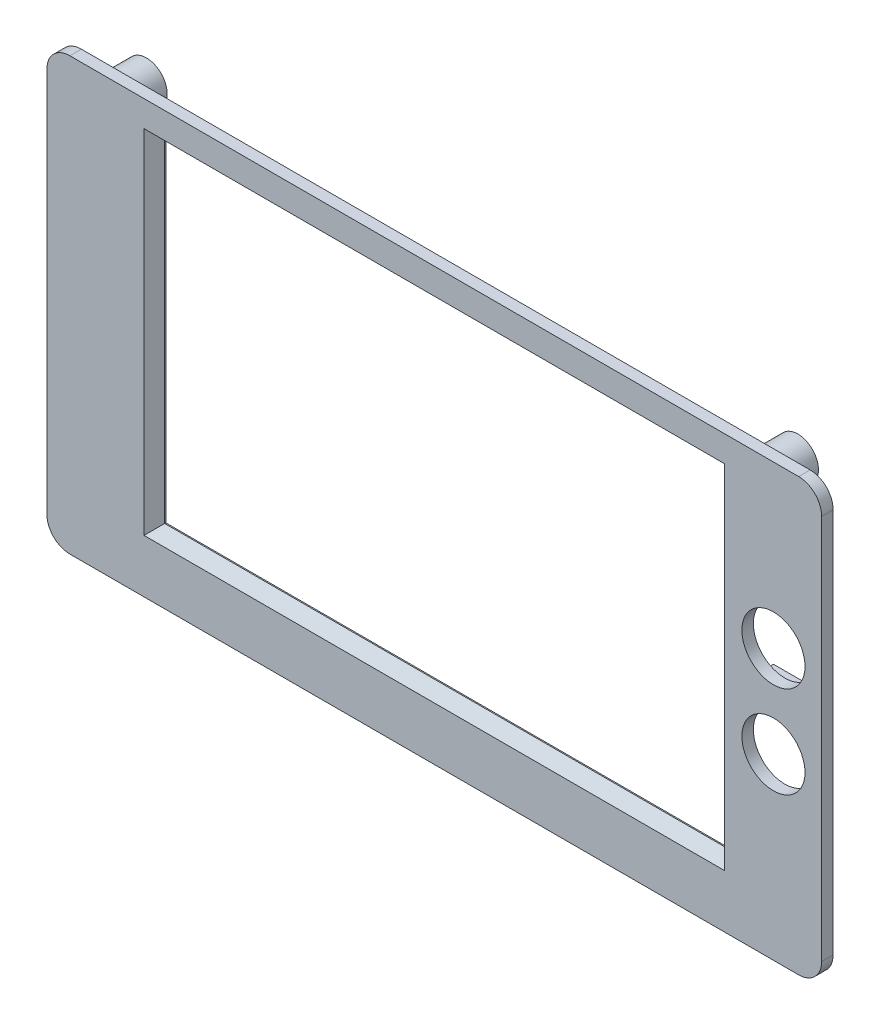
SolidWorks part; units mm, degrees
ref_plane "Спереди" through (0, 0, 0) normal (0, 0, 1) x (1, 0, 0)
ref_plane "Сверху" through (0, 0, 0) normal (0, 1, 0) x (1, 0, 0)
ref_plane "Справа" through (0, 0, 0) normal (1, 0, 0) x (0, 0, -1)
sketch "Эскиз2" plane through (0, 0, 0) normal (0, 0, 1) x (1, 0, 0)
  line L0 (47.98, -25.72) -> (47.98, 30.47)
  line L1 (47.98, 30.47) -> (-47.98, 30.47)
  line L2 (-47.98, 30.47) -> (-47.98, -25.72)
  line L3 (-47.98, -25.72) -> (47.98, -25.72)
  line L4 (-52.73, -33.72) -> (52.73, -33.72)
  line L5 (-52.73, 33.72) -> (-52.73, -33.72)
  line L6 (52.73, 33.72) -> (-52.73, 33.72)
  line L7 (52.73, -33.72) -> (52.73, 33.72)
  line L8 (57.5, 37) -> (-57.5, 37)
  line L9 (60, -34.5) -> (60, 34.5)
  line L10 (-60, 34.5) -> (-60, -34.5)
  line L11 (-57.5, -37) -> (57.5, -37)
  circle A0 centre (56.75, 33.75) radius 1.6
  circle A1 centre (56.75, -33.75) radius 1.6
  arc A2 (60, 34.5) -> (57.5, 37) centre (57.5, 34.5) ccw
  arc A3 (-57.5, 37) -> (-60, 34.5) centre (-57.5, 34.5) ccw
  circle A4 centre (-56.75, 33.75) radius 1.6
  arc A5 (-60, -34.5) -> (-57.5, -37) centre (-57.5, -34.5) ccw
  circle A6 centre (-56.75, -33.75) radius 1.6
  arc A7 (57.5, -37) -> (60, -34.5) centre (57.5, -34.5) ccw
sketch "Эскиз3" plane through (0, 0, 0) normal (0, 0, 1) x (1, 0, 0)
  line L0 (-57.5, -37) -> (57.5, -37) construction
  line L1 (-60, 34.5) -> (-60, -34.5) construction
  line L2 (57.5, 37) -> (-57.5, 37) construction
  line L3 (60, -34.5) -> (60, 34.5) construction
  line L4 (-47.98, -25.72) -> (47.98, -25.72) construction
  line L5 (47.98, -25.72) -> (47.98, 30.47) construction
  line L6 (47.98, 30.47) -> (-47.98, 30.47) construction
  line L7 (-47.98, 30.47) -> (-47.98, -25.72) construction
  line L8 (-57.5, -37) -> (57.5, -37)
  line L9 (-60, 34.5) -> (-60, -34.5)
  line L10 (57.5, 37) -> (-57.5, 37)
  line L11 (60, -34.5) -> (60, 34.5)
  line L12 (-47.98, -25.72) -> (47.98, -25.72)
  line L13 (47.98, -25.72) -> (47.98, 30.47)
  line L14 (47.98, 30.47) -> (-47.98, 30.47)
  line L15 (-47.98, 30.47) -> (-47.98, -25.72)
  arc A0 (-60, -34.5) -> (-57.5, -37) centre (-57.5, -34.5) ccw construction
  arc A1 (-60, -34.5) -> (-57.5, -37) centre (-57.5, -34.5) ccw
  arc A2 (57.5, -37) -> (60, -34.5) centre (57.5, -34.5) ccw construction
  arc A3 (57.5, -37) -> (60, -34.5) centre (57.5, -34.5) ccw
  arc A4 (60, 34.5) -> (57.5, 37) centre (57.5, 34.5) ccw construction
  arc A5 (60, 34.5) -> (57.5, 37) centre (57.5, 34.5) ccw
  arc A6 (-57.5, 37) -> (-60, 34.5) centre (-57.5, 34.5) ccw construction
  arc A7 (-57.5, 37) -> (-60, 34.5) centre (-57.5, 34.5) ccw
extrude "Бобышка-Вытянуть2" add sketch "Эскиз3" along normal blind 2
sketch "Эскиз4" plane through (0, 0, 2) normal (0, 0, 1) x (1, 0, 0)
  line L0 (-47.98, 30.47) -> (-47.98, -25.72) construction
  line L1 (-47.98, -25.72) -> (47.98, -25.72) construction
  line L2 (47.98, -25.72) -> (47.98, 30.47) construction
  line L3 (47.98, 30.47) -> (-47.98, 30.47) construction
  line L4 (-47.98, 30.47) -> (-47.98, -25.72)
  line L5 (-47.98, -25.72) -> (47.98, -25.72)
  line L6 (47.98, -25.72) -> (47.98, 30.47)
  line L7 (47.98, 30.47) -> (-47.98, 30.47)
extrude "Вырез-Вытянуть-Тонкостенный1" cut sketch "Эскиз4" against normal blind 2 thin thin type one direction wall 0.8
sketch "Эскиз5" plane through (0, 0, 0) normal (0, 0, -1) x (-1, 0, 0)
  circle A0 centre (56.75, 33.75) radius 2.4
  circle A1 centre (-56.75, 33.75) radius 2.4
  circle A2 centre (-56.75, -33.75) radius 2.4
  circle A3 centre (56.75, -33.75) radius 2.4
  dimension "D1" = 4.8
extrude "Вытянуть-Тонкостенный1" add sketch "Эскиз5" along normal blind 4.6 thin thin type one direction wall 1.2
sketch "Эскиз7" plane through (0, 0, 2) normal (0, 0, 1) x (1, 0, 0)
  line L4 (-57.5, -37) -> (57.5, -37)
  line L5 (60, -34.5) -> (60, 34.5)
  line L6 (57.5, 37) -> (-57.5, 37)
  line L7 (-60, 34.5) -> (-60, -34.5)
  line L8 (-57.5, -37) -> (57.5, -37)
  line L9 (60, -34.5) -> (60, 34.5)
  line L10 (57.5, 37) -> (-57.5, 37)
  line L11 (-60, 34.5) -> (-60, -34.5)
  arc A4 (-60, -34.5) -> (-57.5, -37) centre (-57.5, -34.5) ccw
  arc A5 (57.5, -37) -> (60, -34.5) centre (57.5, -34.5) ccw
  arc A6 (60, 34.5) -> (57.5, 37) centre (57.5, 34.5) ccw
  arc A7 (-57.5, 37) -> (-60, 34.5) centre (-57.5, 34.5) ccw
  arc A8 (-60, -34.5) -> (-57.5, -37) centre (-57.5, -34.5) ccw
  arc A9 (57.5, -37) -> (60, -34.5) centre (57.5, -34.5) ccw
  arc A10 (60, 34.5) -> (57.5, 37) centre (57.5, 34.5) ccw
  arc A11 (-57.5, 37) -> (-60, 34.5) centre (-57.5, 34.5) ccw
  dimension "D1" = 0
extrude "Вытянуть-Тонкостенный3" add sketch "Эскиз7" against normal blind 2 thin thin type one direction wall 0.6
chamfer "Фаска1" distance 1.8 angle 45 4 edges at (0, -26.52, 2) (48.78, 2.375, 2) (0, 31.27, 2) (-48.78, 2.375, 2)
sketch "Эскиз8" plane through (0, 0, 2) normal (0, 0, 1) x (1, 0, 0)
  line L1 (57.5, 37.6) -> (67.5, 37.6)
  line L2 (57.5, 37.6) -> (57.5, -37.6)
  line L3 (57.5, -37.6) -> (67.5, -37.6)
  line L4 (67.5, 37.6) -> (67.5, -37.6)
  line L5 (-57.5, 37.6) -> (-67.5, 37.6)
  line L6 (-57.5, 37.6) -> (-57.5, -37.6)
  line L7 (-57.5, -37.6) -> (-67.5, -37.6)
  line L8 (-67.5, 37.6) -> (-67.5, -37.6)
  dimension "D1" = 10
  dimension "D2" = 10
extrude "Бобышка-Вытянуть3" add sketch "Эскиз8" against normal blind 2
fillet "Скругление1" radius 4 4 edges at (67.5, -37.6, 1) (-67.5, -37.6, 1) (67.5, 37.6, 1) (-67.5, 37.6, 1)
sketch "Эскиз9" plane through (0, 0, 2) normal (0, 0, 1) x (1, 0, 0)
  line L0 (67.5, -33.6) -> (67.5, 33.6) construction
  line L1 (-48.78, -26.52) -> (48.78, -26.52) construction
  circle A0 centre (59.1, 9.48) radius 5.5
  circle A1 centre (59.1, -6.52) radius 5.5
  dimension "D1" = 11
  dimension "D2" = 11
  dimension "D3" = 8.4
  dimension "D4" = 8.4
  dimension "D5" = 16
  dimension "D6" = 20
extrude "Вырез-Вытянуть1" cut sketch "Эскиз9" against normal blind 2
sketch "Эскиз11" plane through (0, 0, 0) normal (0, 0, -1) x (-1, 0, 0)
  circle A1 centre (-56.75, 33.75) radius 2.4
  circle A2 centre (-56.75, 33.75) radius 2.4
  circle A3 centre (56.75, 33.75) radius 2.4
  circle A4 centre (56.75, 33.75) radius 2.4
  circle A5 centre (56.75, -33.75) radius 2.4
  circle A6 centre (56.75, -33.75) radius 2.4
  circle A7 centre (-56.75, -33.75) radius 2.4
  circle A8 centre (-56.75, -33.75) radius 2.4
  dimension "D1" = 0
  dimension "D2" = 0
  dimension "D3" = 0
  dimension "D4" = 0
extrude "Вытянуть-Тонкостенный4" add sketch "Эскиз11" along normal blind 4.6 thin thin type one direction reverse wall 1.4
sketch "Эскиз14" plane through (0, 0, 0) normal (0, 0, -1) x (-1, 0, 0)
  line L1 (-64.1, 18.48) -> (-54.1, 18.48)
  line L2 (-64.1, 18.48) -> (-64.1, 17.48)
  line L3 (-64.1, 17.48) -> (-54.1, 17.48)
  line L4 (-54.1, 18.48) -> (-54.1, 17.48)
  line L5 (-64.1, 2.08) -> (-54.1, 2.08)
  line L6 (-64.1, 2.08) -> (-64.1, 1.08)
  line L7 (-64.1, 1.08) -> (-54.1, 1.08)
  line L8 (-54.1, 2.08) -> (-54.1, 1.08)
  line L9 (-64.1, -15.52) -> (-54.1, -15.52)
  line L10 (-64.1, -15.52) -> (-64.1, -16.52)
  line L11 (-64.1, -16.52) -> (-54.1, -16.52)
  line L12 (-54.1, -15.52) -> (-54.1, -16.52)
  circle A0 centre (-59.1, 9.48) radius 5.5 construction
  circle A1 centre (-59.1, -6.52) radius 5.5 construction
  dimension "D4" = 7.4
  dimension "D6" = 9
  dimension "D7" = 5
  dimension "D1" = 8
  dimension "D2" = 1
  dimension "D3" = 1
  dimension "D5" = 1
  dimension "D8" = 5
extrude "Бобышка-Вытянуть4" add sketch "Эскиз14" along normal blind 3
chamfer "Фаска2" distance 3 angle 45 1 edges at (59.1, 18.48, 0)
chamfer "Фаска3" distance 3 angle 45 1 edges at (59.1, -16.52, 0)
